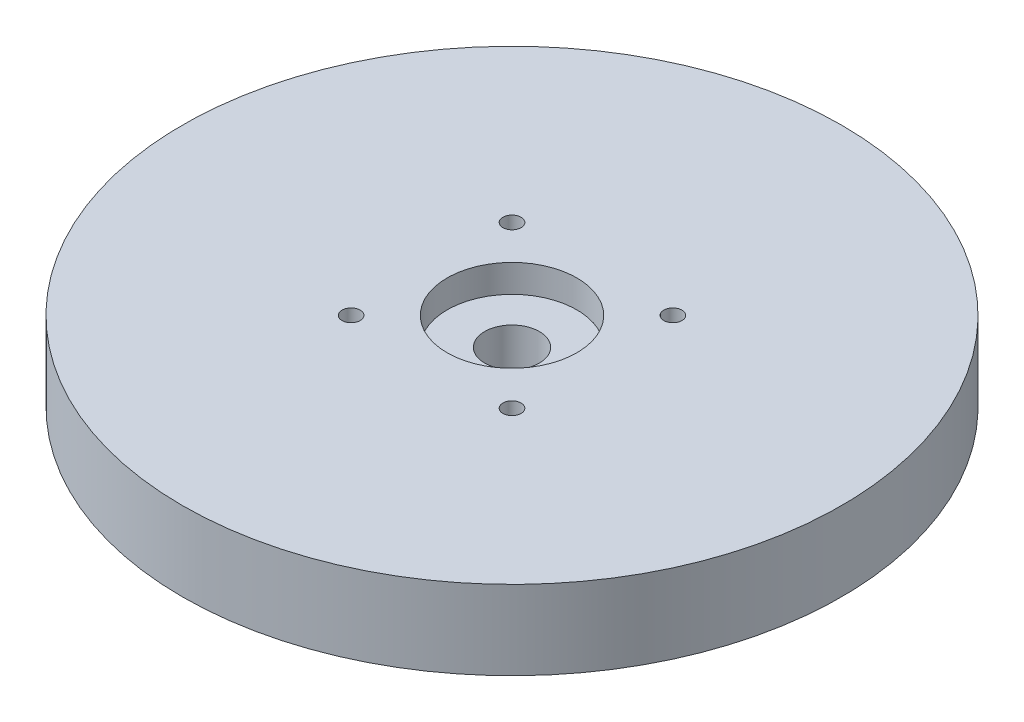
SolidWorks part; units mm, degrees
ref_plane "Front Plane" through (0, 0, 0) normal (0, 0, 1) x (1, 0, 0)
ref_plane "Top Plane" through (0, 0, 0) normal (0, 1, 0) x (1, 0, 0)
ref_plane "Right Plane" through (0, 0, 0) normal (1, 0, 0) x (0, 0, -1)
sketch "Sketch2" plane through (0, 0, 0) normal (0, 1, 0) x (1, 0, 0)
  circle A1 centre (0, 0) radius 63.5
  dimension "D1" = 127
extrude "Boss-Extrude1" add sketch "Sketch2" along normal blind 15.24 contours A1 | A1 | A1 | A1 | A1 | A1 | A1 | A1 | A1 | A1 | A1 | A1 | A1 | A1 | A1 | A1 | A1 | A1 | A1 | A1 | A1 | A1 | A1 | A1 | A1 | A1 | A1 | A1 | A1 | A1 | A1 | A1 | A1 | A1 | A1 | A1 | A1 | A1 | A1 | A1 | A1 | A1 | A1 | A1 | A1 | A1 region at (0, 0, 0)
sketch "Sketch3" plane through (0, 15.24, 0) normal (0, 1, 0) x (1, 0, 0)
  circle A4 centre (0, 0) radius 5.2705
  dimension "D1" = 10.541
extrude "Cut-Extrude3" cut sketch "Sketch3" against normal through all contours A4 region at (0, 15.24, 0)
sketch "Sketch4" plane through (0, 15.24, 0) normal (0, 1, 0) x (1, 0, 0)
  line L0 (-15.5, -15.5) -> (15.5, 15.5) construction
  circle A0 centre (-15.5, 15.5) radius 1.75
  circle A1 centre (15.5, 15.5) radius 1.75
  circle A2 centre (15.5, -15.5) radius 1.75
  circle A3 centre (-15.5, -15.5) radius 1.75
  point P8 (0, 0)
  dimension "D1" = 3.5
  dimension "D5" = 31
  dimension "D6" = 31
extrude "Cut-Extrude4" cut sketch "Sketch4" against normal blind 55.626
sketch "Sketch5" plane through (0, 15.24, 0) normal (0, 1, 0) x (1, 0, 0)
  circle A0 centre (0, 0) radius 12.5
  point P3 (0, 0)
  dimension "D1" = 25
extrude "Cut-Extrude5" cut sketch "Sketch5" against normal blind 5.334
